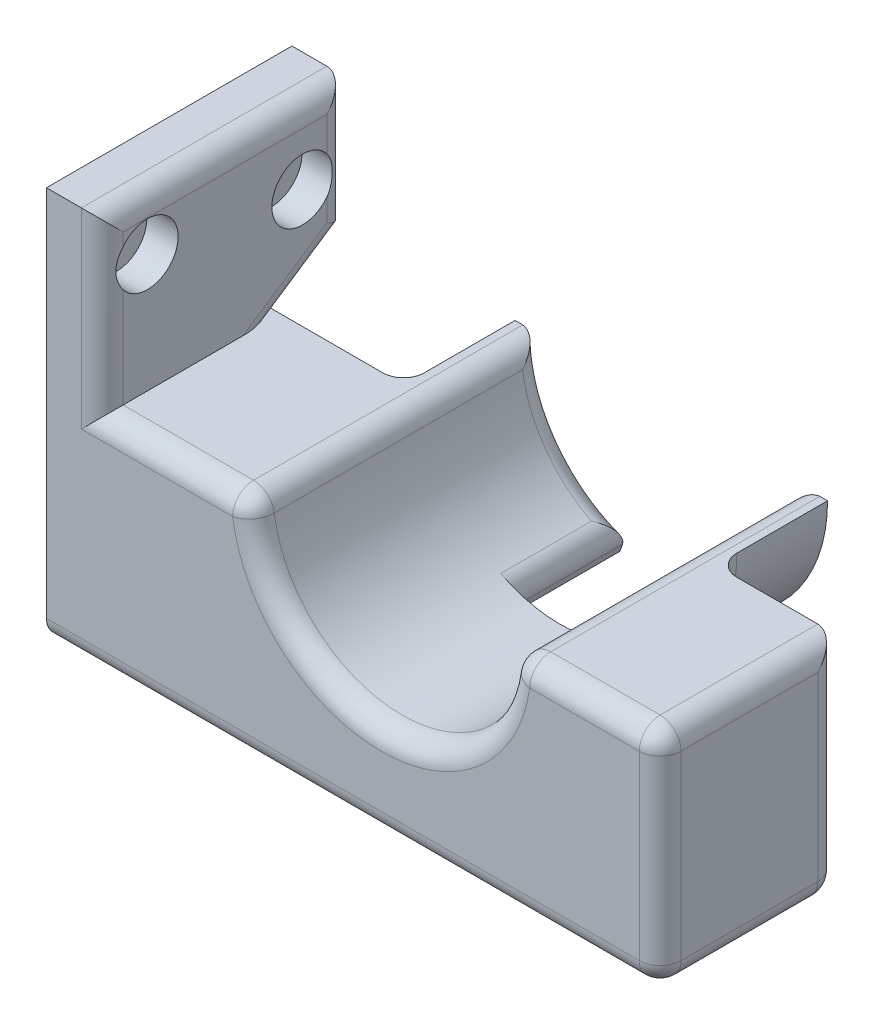
SolidWorks part; units mm, degrees
note: The reader was unsure of these and kept them because the rebuilt part matched: shared geometry of "Sketch1<4>".
ref_plane "Front Plane" through (0, 0, 0) normal (0, 0, 1) x (1, 0, 0)
ref_plane "Top Plane" through (0, 0, 0) normal (0, 1, 0) x (1, 0, 0)
ref_plane "Right Plane" through (0, 0, 0) normal (1, 0, 0) x (0, 0, -1)
sketch "Sketch1" plane through (0, 0, 0) normal (0, 0, 1) x (1, 0, 0)
  line L0 (991.6692, 3803.8817) -> (1011.9892, 3803.8817)
  line L1 (1011.9892, 3803.8817) -> (1023.4192, 3803.8817)
  line L3 (1023.4192, 3803.8817) -> (959.9192, 3803.8817)
  line L4 (1023.4192, 3803.8817) -> (1023.4192, 3778.4817)
  line L5 (1023.4192, 3778.4817) -> (959.9192, 3778.4817)
  line L6 (959.9192, 3803.8817) -> (959.9192, 3778.4817)
  line L12 (986.8389, 3790.0045) -> (985.624, 3786.5141)
  line L13 (996.4995, 3790.0045) -> (997.7144, 3786.5141)
  arc A1 (971.3492, 3803.8817) -> (1011.9892, 3803.8817) centre (991.6692, 3803.8817) ccw
  circle A2 centre (991.6692, 3803.8817) radius 17.78
  arc A3 (976.9753, 3803.8817) -> (1006.3631, 3803.8817) centre (991.6692, 3803.8817) ccw
  arc A7 (973.2796, 3803.8817) -> (1010.0588, 3803.8817) centre (991.6692, 3803.8817) ccw
  point P16 (973.2796, 3803.8817)
  point P18 (1010.0588, 3803.8817)
  point P19 (971.3492, 3803.8817)
  point P26 (1007.6392, 3803.8817)
  point P27 (975.7053, 3803.8817)
  point P28 (996.917, 3788.805)
  point P29 (986.4214, 3788.805)
  point P30 (1007.6331, 3803.8817)
  dimension "D3" = 35.56
  dimension "D1" = 63.5
  dimension "D2" = 25.4
extrude "Boss-Extrude2" add sketch "Sketch1" along normal blind 20.32
extrude "Boss-Extrude3" add sketch "Sketch1<4>" against normal blind 12.7
sketch "Sketch1<4>" plane through (0, 0, 0) normal (0, 0, 1) x (1, 0, 0) same geometry as "Sketch1"
sketch "Sketch3" plane through (959.9192, 0, 0) normal (-1, 0, 0) x (0, 0, 1)
  line L0 (20.32, 3808.9617) -> (20.32, 3803.8817)
  line L1 (15.1754, 3817.359) -> (-2.4754, 3814.9112) construction
  line L2 (20.32, 3808.9617) -> (20.32, 3823.3085)
  line L3 (6.35, 3816.1351) -> (6.35, 3823.3085) construction
  line L4 (20.32, 3803.8817) -> (0, 3803.8817)
  line L5 (0, 3803.8817) -> (0, 3778.4817)
  line L6 (0, 3778.4817) -> (20.32, 3778.4817)
  line L7 (20.32, 3778.4817) -> (20.32, 3803.8817)
  line L8 (20.32, 3803.8817) -> (0, 3803.8817) construction
  line L10 (0, 3778.4817) -> (20.32, 3778.4817) construction
  line L11 (20.32, 3778.4817) -> (20.32, 3803.8817) construction
  line L12 (20.32, 3808.9617) -> (-7.62, 3808.9617)
  line L13 (20.32, 3823.3085) -> (-7.62, 3823.3085)
  line L14 (-7.62, 3808.9617) -> (-7.62, 3823.3085)
  line L15 (20.32, 3808.9617) -> (-7.62, 3823.3085) construction
  line L16 (20.32, 3823.3085) -> (-7.62, 3808.9617) construction
  line L17 (20.32, 3803.8817) -> (20.32, 3778.4817)
  line L18 (20.32, 3803.8817) -> (20.32, 3808.9617)
  line L21 (0, 3803.8817) -> (-7.62, 3808.9617)
  line L24 (0, 3803.8817) -> (0, 3778.4817)
  circle A2 centre (-2.4754, 3814.9112) radius 1.4859
  circle A3 centre (15.1754, 3817.359) radius 1.4859
  point P6 (0, 0)
  point P16 (0, 0)
  dimension "D2" = 2.9718
  dimension "D3" = 27.94
  dimension "D4" = 5.08
  dimension "D5" = 14.3468
  dimension "D1" = 0
extrude "Boss-Extrude4" add sketch "Sketch3" along normal blind 6.35
sketch "Sketch4" plane through (959.9192, 0, 0) normal (1, 0, 0) x (0, 0, -1)
  circle A10 centre (-15.1754, 3817.359) radius 3.4925
  circle A11 centre (2.4754, 3814.9112) radius 3.4925
  circle A12 centre (-15.1754, 3817.359) radius 1.4859 construction
  circle A13 centre (2.4754, 3814.9112) radius 1.4859 construction
  circle A14 centre (-15.1754, 3817.359) radius 1.4859 construction
  circle A15 centre (2.4754, 3814.9112) radius 1.4859 construction
  point P1 (0, 0)
  point P11 (0, 0)
extrude "Cut-Extrude1" cut sketch "Sketch4" against normal blind 3.556
fillet "Fillet9" radius 2.38 6 edges at (996.4995, 3790.0045, -6.35) (986.8389, 3790.0045, -6.35) (979.6924, 3795.369, -12.7) (1003.646, 3795.369, -12.7) (1006.3631, 3803.8817, 3.81) (976.9753, 3803.8817, 3.81)
fillet "Fillet10" radius 2.38 15 edges at (988.4942, 3778.4817, 0) (988.4942, 3778.4817, 20.32) (1023.4192, 3778.4817, 10.16) (1023.4192, 3791.1817, 0) (1023.4192, 3791.1817, 20.32) (1023.4192, 3803.8817, 10.16) (1015.9978, 3803.8817, 20.32) (959.9192, 3806.4217, -3.81) (959.9192, 3816.1351, -7.62) (959.9192, 3823.3085, 6.35) (959.9192, 3813.5951, 20.32) (967.3406, 3803.8817, 20.32) (976.3232, 3803.2981, 20.32) (991.6692, 3789.1878, 20.32) (1007.0152, 3803.2981, 20.32)
fillet "Fillet11" radius 2.38 2 edges at (1006.1615, 3793.5811, 0) (977.177, 3793.5811, 0)
ref_plane "Plane6" through (0, 0, 10.16) normal (0, 0, -1) x (-1, 0, 0)
sketch "Sketch11" plane through (0, 0, 10.16) normal (0, 0, -1) x (-1, 0, 0)
  line L0 (-991.6692, 3803.8817) -> (-991.6692, 3783.5617)
  line L1 (-991.6692, 3803.8817) -> (-1009.2669, 3793.7217)
  line L2 (-991.6692, 3803.8817) -> (-974.0716, 3793.7217)
  arc A0 (-985.8244, 3787.0899) -> (-973.8892, 3803.8817) centre (-991.6692, 3803.8817) ccw construction
  arc A1 (-1009.4492, 3803.8817) -> (-997.514, 3787.0899) centre (-991.6692, 3803.8817) ccw construction
  arc A2 (-985.8244, 3787.0899) -> (-973.8892, 3803.8817) centre (-991.6692, 3803.8817) ccw construction
  arc A3 (-1009.4492, 3803.8817) -> (-997.514, 3787.0899) centre (-991.6692, 3803.8817) ccw construction
  circle A4 centre (-991.6692, 3803.8817) radius 17.78 construction
  circle A5 centre (-991.6692, 3803.8817) radius 20.32
  dimension "D2" = 60
  dimension "D3" = 60
  dimension "D1" = 2.54
ref_plane "Plane7" through (991.6692, 3783.5617, 16.1671) normal (0, 0, 1) x (1, 0, 0)
sketch "Sketch13" plane through (991.6692, 3783.5617, 16.1671) normal (0, 0, 1) x (1, 0, 0)
  line L6 (-14.5941, 4.9577) -> (-20.6012, 15.3623)
  line L7 (-23.1748, 13.8764) -> (-17.1677, 3.4718)
  line L8 (20.6012, 15.3623) -> (14.5941, 4.9577)
  line L9 (17.1677, 3.4718) -> (23.1748, 13.8764)
  line L10 (6.0071, 0) -> (-6.0071, 0)
  line L11 (-6.0071, -2.9718) -> (6.0071, -2.9718)
  line L12 (-23.1748, 13.8764) -> (-20.6012, 15.3623)
  line L13 (-17.1677, 3.4718) -> (-14.5941, 4.9577)
  line L14 (-6.0071, 0) -> (-6.0071, -2.9718)
  line L15 (6.0071, -2.9718) -> (6.0071, 0)
  line L16 (14.5941, 4.9577) -> (17.1677, 3.4718)
  line L17 (20.6012, 15.3623) -> (23.1748, 13.8764)
extrude "Cut-Extrude6" cut sketch "Sketch13" along direction (0, 0, -1) on the side against the normal blind 22.86
